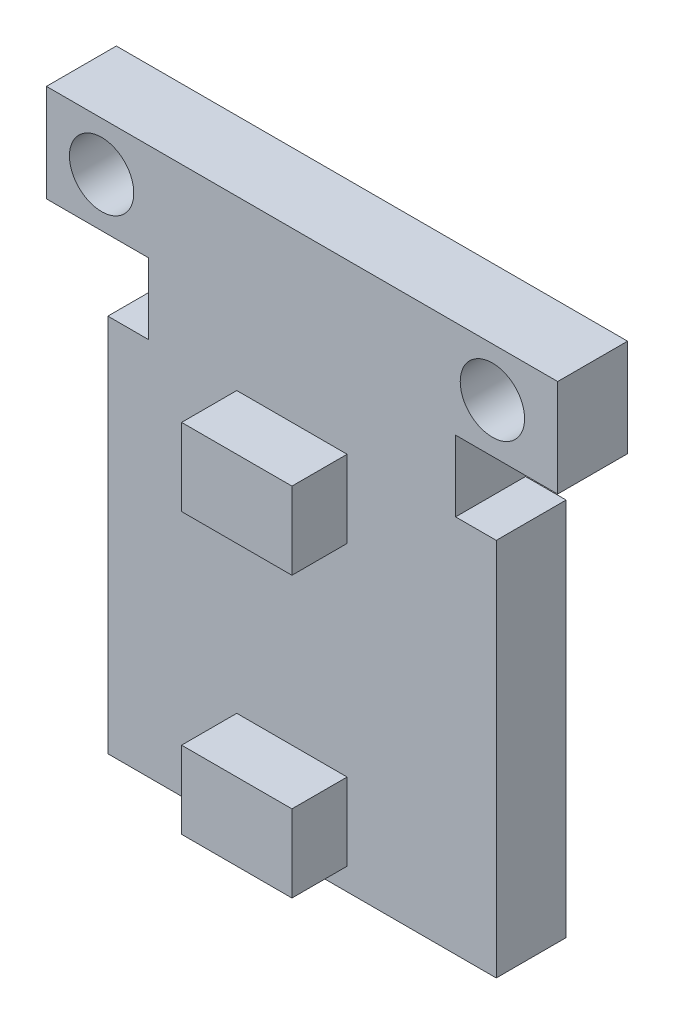
SolidWorks part; units mm, degrees
ref_plane "Front Plane" through (0, 0, 0) normal (0, 0, 1) x (1, 0, 0)
ref_plane "Top Plane" through (0, 0, 0) normal (0, 1, 0) x (1, 0, 0)
ref_plane "Right Plane" through (0, 0, 0) normal (1, 0, 0) x (0, 0, -1)
sketch "Sketch1" plane through (0, 0, 0) normal (0, 0, 1) x (1, 0, 0)
  line L0 (-13.9, 0) -> (13.9, 0)
  line L1 (-13.9, 0) -> (-13.9, -5.3)
  line L2 (13.9, 0) -> (13.9, -5.3)
  line L3 (-13.9, -5.3) -> (-8.35, -5.3)
  line L4 (13.9, -5.3) -> (8.35, -5.3)
  line L5 (-8.35, -5.3) -> (-8.35, -9.15)
  line L6 (8.35, -5.3) -> (8.35, -9.15)
  line L7 (-8.35, -9.15) -> (-10.56, -9.15)
  line L8 (-10.56, -9.15) -> (-10.56, -29.76)
  line L9 (-10.56, -29.76) -> (9.69, -29.76)
  line L11 (10.56, -9.15) -> (8.35, -9.15)
  line L12 (10.56, -9.15) -> (10.56, -29.76)
  line L13 (10.56, -29.76) -> (9.69, -29.76)
  line L14 (-13.9, -2.65) -> (13.9, -2.65) construction
  circle A0 centre (-10.9, -2.65) radius 1.75
  circle A1 centre (10.35, -2.65) radius 1.75
  point P3 (0, 0)
  point P21 (0, 0)
  point P22 (0, 0)
  point P23 (0, 0)
  dimension "D12" = 3.5
  dimension "D1" = 27.8
  dimension "D2" = 5.3
  dimension "D3" = 5.55
  dimension "D4" = 5.55
  dimension "D5" = 3.85
  dimension "D6" = 3.85
  dimension "D7" = 20.61
  dimension "D8" = 20.25
  dimension "D9" = 2.21
  dimension "D10" = 2.21
  dimension "D11" = 3
  dimension "D13" = 21.25
extrude "Boss-Extrude1" add sketch "Sketch1" along normal blind 3.8
sketch "Sketch2" plane through (0, 0, 3.8) normal (0, 0, 1) x (1, 0, 0)
  line L0 (-8.35, -9.15) -> (8.35, -9.15) construction
  line L2 (-3.55, -9.15) -> (2.45, -9.15)
  line L3 (-3.55, -9.15) -> (-3.55, -13.35)
  line L4 (-3.55, -13.35) -> (2.45, -13.35)
  line L5 (2.45, -9.15) -> (2.45, -13.35)
  line L6 (-3.55, -28.55) -> (2.45, -28.55)
  line L7 (-3.55, -28.55) -> (-3.55, -24.35)
  line L8 (-3.55, -24.35) -> (2.45, -24.35)
  line L9 (2.45, -28.55) -> (2.45, -24.35)
  circle A0 centre (-10.9, -2.65) radius 1.75 construction
  dimension "D5" = 7.35
  dimension "D1" = 4.2
  dimension "D2" = 4.2
  dimension "D3" = 6
  dimension "D4" = 6
  dimension "D6" = 11
extrude "Boss-Extrude2" add sketch "Sketch2" along normal blind 3
sketch "Sketch3" plane through (0, 0, 0) normal (0, 0, -1) x (-1, 0, 0)
  text T0 "OLED\r\nSCREEN"
  point P1 (-8.0257, -18.6161)
  point P2 (-8.8283, -18.6438)
extrude "Cut-Extrude1" cut sketch "Sketch3" against normal blind 1.2
